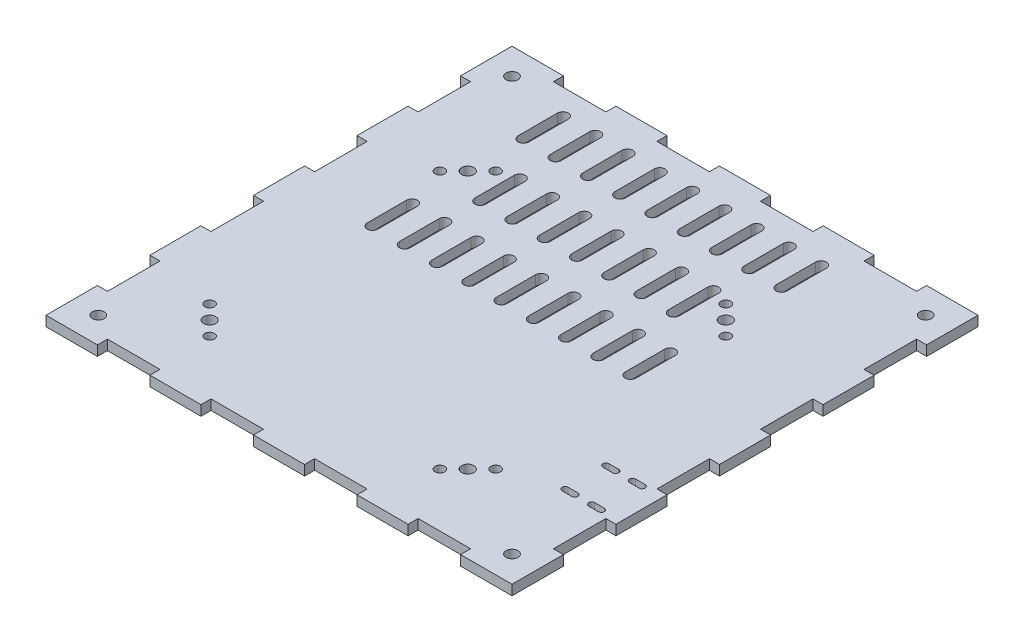
SolidWorks part; units mm, degrees
material "Acrylic (Medium-high impact)"
ref_plane "Front Plane" through (0, 0, 0) normal (0, 0, 1) x (1, 0, 0)
ref_plane "Top Plane" through (0, 0, 0) normal (0, 1, 0) x (1, 0, 0)
ref_plane "Right Plane" through (0, 0, 0) normal (1, 0, 0) x (0, 0, -1)
sketch "Board refrence" plane through (0, 0, 0) normal (0, 1, 0) x (1, 0, 0)
  line L0 (42.5, -17.26) -> (47.5, -17.26)
  line L1 (-40, -40) -> (40, -40)
  line L2 (-40, -40) -> (-40, 40)
  line L3 (-40, 40) -> (40, 40)
  line L4 (40, -40) -> (40, 40)
  line L5 (-40, -40) -> (40, 40) construction
  line L6 (-40, 40) -> (40, -40) construction
  line L7 (-50.8, 46.35) -> (50.8, 46.35)
  line L8 (-50.8, 46.35) -> (-50.8, 40)
  line L9 (-50.8, 40) -> (50.8, 40)
  line L10 (50.8, 46.35) -> (50.8, 40)
  line L11 (42.5, -25.26) -> (47.5, -25.26)
  line L12 (45, -25.26) -> (45, -17.26) construction
  circle A0 centre (-36, 36) radius 1.6
  circle A1 centre (-36, -36) radius 1.6
  circle A2 centre (36, -36) radius 1.6
  circle A3 centre (36, 36) radius 1.6
  point P0 (0, 0)
  point P14 (0, 40)
  point P15 (0, 40)
  point P26 (45, -21.26)
  dimension "D4" = 3.2
  dimension "D1" = 80
  dimension "D2" = 80
  dimension "D3" = 4
  dimension "D5" = 6.35
  dimension "D6" = 101.6
  dimension "D7" = 18.74
  dimension "D8" = 8
  dimension "D9" = 5
  dimension "D10" = 5
sketch "Sketch2" plane through (0, 0, 0) normal (0, 1, 0) x (1, 0, 0)
  line L0 (-40, -40) -> (-40, 40) construction
  line L1 (-56.8, 69.15) -> (66.8, 69.15) construction
  line L2 (-56.8, 69.15) -> (-56.8, -54.45) construction
  line L3 (-56.8, -54.45) -> (66.8, -54.45) construction
  line L4 (66.8, 69.15) -> (66.8, -54.45) construction
  line L6 (40, -40) -> (40, 40) construction
  line L7 (-50.8, 46.35) -> (50.8, 46.35) construction
  line L8 (-60, 72.35) -> (-60, -57.65)
  line L9 (-60, -57.65) -> (70, -57.65)
  line L10 (70, 72.35) -> (70, -57.65)
  line L11 (-60, 72.35) -> (70, 72.35)
  circle A0 centre (-36, 36) radius 1.7
  circle A1 centre (-36, -36) radius 1.7
  circle A2 centre (36, -36) radius 1.7
  circle A3 centre (36, 36) radius 1.7
  point P16 (0, 0)
  dimension "D1" = 3.4
  dimension "D2" = 20
  dimension "D3" = 26
  dimension "D4" = 30
  dimension "D6" = 130
  dimension "D7" = 130
  dimension "D5" = 3.2
extrude "Boss-Extrude1" add sketch "Sketch2" along normal blind 2.8
sketch "Sketch5" plane through (0, 2.8, 0) normal (0, 1, 0) x (1, 0, 0)
  line L0 (32.1109, 39.8891) -> (39.8891, 32.1109) construction
  line L1 (70, -57.65) -> (70, 72.35) construction
  circle A0 centre (39.8891, 32.1109) radius 1.35
  circle A1 centre (32.1109, 39.8891) radius 1.35
  circle A2 centre (32.1109, -39.8891) radius 1.35
  circle A3 centre (39.8891, -32.1109) radius 1.35
  circle A4 centre (-39.8891, -32.1109) radius 1.35
  circle A5 centre (-32.1109, -39.8891) radius 1.35
  circle A6 centre (-32.1109, 39.8891) radius 1.35
  circle A7 centre (-39.8891, 32.1109) radius 1.35
  point P4 (36, 36)
  point P23 (0, 0)
  dimension "D3" = 2.7
  dimension "D1" = 45
  dimension "D2" = 11
extrude "Cut-Extrude2" cut sketch "Sketch5" against normal up to next
sketch "Sketch4" plane through (0, 2.8, 0) normal (0, 1, 0) x (1, 0, 0)
  line L0 (70, 57.9056) -> (70, 43.4611)
  line L1 (70, -57.65) -> (70, 72.35) construction
  line L2 (70, 14.5722) -> (67.2, 14.5722)
  line L3 (67.2, 14.5722) -> (67.2, 29.0167)
  line L4 (67.2, 29.0167) -> (70, 29.0167)
  line L5 (70, 29.0167) -> (70, 14.5722)
  line L6 (70, -14.3167) -> (67.2, -14.3167)
  line L7 (67.2, -14.3167) -> (67.2, 0.1278)
  line L8 (67.2, 0.1278) -> (70, 0.1278)
  line L9 (70, 0.1278) -> (70, -14.3167)
  line L10 (70, 43.4611) -> (67.2, 43.4611)
  line L11 (67.2, 43.4611) -> (67.2, 57.9056)
  line L12 (67.2, 57.9056) -> (70, 57.9056)
  line L13 (70, -43.2056) -> (67.2, -43.2056)
  line L14 (67.2, -43.2056) -> (67.2, -28.7611)
  line L15 (67.2, -28.7611) -> (70, -28.7611)
  line L16 (70, -28.7611) -> (70, -43.2056)
  line L17 (70, 43.4611) -> (70, 14.5722) construction
  line L18 (67.2, -43.2056) -> (67.2, -57.65) construction
  line L19 (-60, -57.65) -> (70, -57.65) construction
  line L20 (67.2, -28.7611) -> (67.2, -14.3167) construction
  line L21 (70, 72.35) -> (-60, 72.35) construction
  line L42 (-60, 72.35) -> (70, -57.65) construction
  line L66 (-45.5556, -57.65) -> (-45.5556, -54.85)
  line L67 (-45.5556, -54.85) -> (-31.1111, -54.85)
  line L68 (-31.1111, -54.85) -> (-31.1111, -57.65)
  line L91 (67.2, 0.1278) -> (67.2, 14.5722) construction
  line L92 (67.2, 29.0167) -> (67.2, 43.4611) construction
  line L93 (67.2, 57.9056) -> (67.2, 72.35) construction
  line L94 (-31.1111, -57.65) -> (-45.5556, -57.65)
  line L95 (-16.6667, -57.65) -> (-16.6667, -54.85)
  line L96 (-16.6667, -54.85) -> (-2.2222, -54.85)
  line L97 (-2.2222, -54.85) -> (-2.2222, -57.65)
  line L103 (-2.2222, -57.65) -> (-16.6667, -57.65)
  line L108 (12.2222, -57.65) -> (12.2222, -54.85)
  line L113 (12.2222, -54.85) -> (26.6667, -54.85)
  line L118 (26.6667, -54.85) -> (26.6667, -57.65)
  line L119 (26.6667, -57.65) -> (12.2222, -57.65)
  line L120 (55.5556, -57.65) -> (41.1111, -57.65)
  line L121 (41.1111, -57.65) -> (41.1111, -54.85)
  line L125 (41.1111, -54.85) -> (55.5556, -54.85)
  line L126 (55.5556, -54.85) -> (55.5556, -57.65)
  line L127 (-60, 57.9056) -> (-57.2, 57.9056)
  line L128 (-57.2, 57.9056) -> (-57.2, 43.4611)
  line L129 (-57.2, 43.4611) -> (-60, 43.4611)
  line L130 (-60, 43.4611) -> (-60, 57.9056)
  line L131 (-60, 29.0167) -> (-57.2, 29.0167)
  line L132 (-57.2, 29.0167) -> (-57.2, 14.5722)
  line L133 (-57.2, 14.5722) -> (-60, 14.5722)
  line L134 (-60, 14.5722) -> (-60, 29.0167)
  line L135 (-60, 0.1278) -> (-57.2, 0.1278)
  line L136 (-57.2, 0.1278) -> (-57.2, -14.3167)
  line L137 (-57.2, -14.3167) -> (-60, -14.3167)
  line L138 (-60, -14.3167) -> (-60, 0.1278)
  line L139 (-60, -43.2056) -> (-60, -28.7611)
  line L140 (-60, -28.7611) -> (-57.2, -28.7611)
  line L141 (-57.2, -28.7611) -> (-57.2, -43.2056)
  line L142 (-57.2, -43.2056) -> (-60, -43.2056)
  line L143 (55.5556, 72.35) -> (55.5556, 69.55)
  line L144 (55.5556, 69.55) -> (41.1111, 69.55)
  line L145 (41.1111, 69.55) -> (41.1111, 72.35)
  line L146 (41.1111, 72.35) -> (55.5556, 72.35)
  line L147 (26.6667, 72.35) -> (26.6667, 69.55)
  line L148 (26.6667, 69.55) -> (12.2222, 69.55)
  line L149 (12.2222, 69.55) -> (12.2222, 72.35)
  line L150 (12.2222, 72.35) -> (26.6667, 72.35)
  line L151 (-2.2222, 72.35) -> (-2.2222, 69.55)
  line L152 (-2.2222, 69.55) -> (-16.6667, 69.55)
  line L153 (-16.6667, 69.55) -> (-16.6667, 72.35)
  line L154 (-16.6667, 72.35) -> (-2.2222, 72.35)
  line L155 (-45.5556, 72.35) -> (-31.1111, 72.35)
  line L156 (-31.1111, 72.35) -> (-31.1111, 69.55)
  line L157 (-31.1111, 69.55) -> (-45.5556, 69.55)
  line L158 (-45.5556, 69.55) -> (-45.5556, 72.35)
  point P27 (5, 7.35)
  point P81 (5, 7.35)
  dimension "D4" = 2.8
  dimension "D1" = 4
  dimension "D2" = 4
extrude "Cut tabs" cut sketch "Sketch4" against normal through all
sketch "Pad reference" plane through (0, 2.8, 0) normal (0, 1, 0) x (1, 0, 0)
  line L2 (-60, -57.65) -> (-45.5556, -57.65) construction
  line L3 (55, 57.35) -> (-45, 57.35) construction
  line L4 (55, 57.35) -> (55, -42.65) construction
  line L5 (55, -42.65) -> (-45, -42.65) construction
  line L7 (-45, 57.35) -> (-45, -42.65) construction
  line L151 (70, -57.65) -> (70, -43.2056) construction
  line L152 (70, 72.35) -> (55.5556, 72.35) construction
  circle A0 centre (-45, 57.35) radius 4
  circle A1 centre (55, 57.35) radius 4
  circle A2 centre (55, -42.65) radius 4
  circle A3 centre (-45, -42.65) radius 4
  dimension "D1" = 8
  dimension "D3" = 15
  dimension "D4" = 15
  dimension "D2" = 15
sketch "Sketch6" plane through (0, 2.8, 0) normal (0, 1, 0) x (1, 0, 0)
  line L0 (64.5, -27.2389) -> (61.8, -27.2389) construction
  line L1 (64.5, -28.0889) -> (61.8, -28.0889)
  line L2 (64.5, -26.3889) -> (61.8, -26.3889)
  line L3 (57.1, -27.2389) -> (54.4, -27.2389) construction
  line L4 (57.1, -28.0889) -> (54.4, -28.0889)
  line L5 (57.1, -26.3889) -> (54.4, -26.3889)
  line L6 (72.5, -21.5389) -> (-49927.5, -21.5389) construction
  line L7 (70, -28.7611) -> (70, -14.3167) construction
  line L8 (57.1, -15.8389) -> (54.4, -15.8389) construction
  line L9 (57.1, -14.9889) -> (54.4, -14.9889)
  line L10 (57.1, -16.6889) -> (54.4, -16.6889)
  line L11 (64.5, -15.8389) -> (61.8, -15.8389) construction
  line L12 (64.5, -14.9889) -> (61.8, -14.9889)
  line L13 (64.5, -16.6889) -> (61.8, -16.6889)
  arc A0 (64.5, -28.0889) -> (64.5, -26.3889) centre (64.5, -27.2389) ccw
  arc A1 (61.8, -26.3889) -> (61.8, -28.0889) centre (61.8, -27.2389) ccw
  arc A2 (57.1, -28.0889) -> (57.1, -26.3889) centre (57.1, -27.2389) ccw
  arc A3 (54.4, -26.3889) -> (54.4, -28.0889) centre (54.4, -27.2389) ccw
  arc A4 (57.1, -14.9889) -> (57.1, -16.6889) centre (57.1, -15.8389) cw
  arc A5 (54.4, -16.6889) -> (54.4, -14.9889) centre (54.4, -15.8389) cw
  arc A6 (64.5, -14.9889) -> (64.5, -16.6889) centre (64.5, -15.8389) cw
  arc A7 (61.8, -16.6889) -> (61.8, -14.9889) centre (61.8, -15.8389) cw
  point P2 (63.15, -27.2389)
  point P7 (55.75, -27.2389)
  point P18 (70, -21.5389)
  point P21 (55.75, -15.8389)
  point P28 (63.15, -15.8389)
  dimension "D3" = 3
  dimension "D1" = 4.4
  dimension "D2" = 1.7
  dimension "D4" = 4.85
  dimension "D5" = 5.5
extrude "Power cord slots" cut sketch "Sketch6" against normal up to next
sketch "Sketch7" plane through (0, 2.8, 0) normal (0, 1, 0) x (1, 0, 0)
  line L0 (-36, 62.55) -> (-36, 51.55) construction
  line L1 (-34.5, 62.55) -> (-34.5, 51.55)
  line L2 (-37.5, 62.55) -> (-37.5, 51.55)
  line L3 (-45.5556, 69.55) -> (-31.1111, 69.55) construction
  line L4 (-37.5, 20.45) -> (-37.5, 9.45)
  line L5 (-28.5, 62.55) -> (-28.5, 51.55)
  line L6 (-25.5, 62.55) -> (-25.5, 51.55)
  line L7 (-27, 62.55) -> (-27, 51.55) construction
  line L8 (-19.5, 62.55) -> (-19.5, 51.55)
  line L9 (-16.5, 62.55) -> (-16.5, 51.55)
  line L10 (-18, 62.55) -> (-18, 51.55) construction
  line L11 (-10.5, 62.55) -> (-10.5, 51.55)
  line L12 (-7.5, 62.55) -> (-7.5, 51.55)
  line L13 (-9, 62.55) -> (-9, 51.55) construction
  line L14 (-1.5, 62.55) -> (-1.5, 51.55)
  line L15 (1.5, 62.55) -> (1.5, 51.55)
  line L16 (0, 62.55) -> (0, 51.55) construction
  line L17 (7.5, 62.55) -> (7.5, 51.55)
  line L18 (10.5, 62.55) -> (10.5, 51.55)
  line L19 (9, 62.55) -> (9, 51.55) construction
  line L20 (16.5, 62.55) -> (16.5, 51.55)
  line L21 (19.5, 62.55) -> (19.5, 51.55)
  line L22 (18, 62.55) -> (18, 51.55) construction
  line L23 (25.5, 62.55) -> (25.5, 51.55)
  line L24 (28.5, 62.55) -> (28.5, 51.55)
  line L25 (27, 62.55) -> (27, 51.55) construction
  line L26 (34.5, 62.55) -> (34.5, 51.55)
  line L27 (37.5, 62.55) -> (37.5, 51.55)
  line L28 (36, 62.55) -> (36, 51.55) construction
  line L32 (-36, 36) -> (-36, 51.55) construction
  line L33 (-36, 36) -> (-36, 20.45) construction
  line L34 (-34.5, 20.45) -> (-34.5, 9.45)
  line L37 (-28.5, 41.5) -> (-28.5, 30.5)
  line L38 (-25.5, 41.5) -> (-25.5, 30.5)
  line L39 (-27, 41.5) -> (-27, 30.5) construction
  line L40 (-19.5, 41.5) -> (-19.5, 30.5)
  line L41 (-16.5, 41.5) -> (-16.5, 30.5)
  line L42 (-18, 41.5) -> (-18, 30.5) construction
  line L43 (-10.5, 41.5) -> (-10.5, 30.5)
  line L44 (-7.5, 41.5) -> (-7.5, 30.5)
  line L45 (-9, 41.5) -> (-9, 30.5) construction
  line L46 (-1.5, 41.5) -> (-1.5, 30.5)
  line L47 (1.5, 41.5) -> (1.5, 30.5)
  line L48 (0, 41.5) -> (0, 30.5) construction
  line L49 (7.5, 41.5) -> (7.5, 30.5)
  line L50 (10.5, 41.5) -> (10.5, 30.5)
  line L51 (9, 41.5) -> (9, 30.5) construction
  line L52 (16.5, 41.5) -> (16.5, 30.5)
  line L53 (19.5, 41.5) -> (19.5, 30.5)
  line L54 (18, 41.5) -> (18, 30.5) construction
  line L55 (25.5, 41.5) -> (25.5, 30.5)
  line L56 (28.5, 41.5) -> (28.5, 30.5)
  line L57 (27, 41.5) -> (27, 30.5) construction
  line L63 (-36, 20.45) -> (-36, 9.45) construction
  line L64 (-28.5, 20.45) -> (-28.5, 9.45)
  line L65 (-25.5, 20.45) -> (-25.5, 9.45)
  line L66 (-27, 20.45) -> (-27, 9.45) construction
  line L67 (-19.5, 20.45) -> (-19.5, 9.45)
  line L68 (-16.5, 20.45) -> (-16.5, 9.45)
  line L69 (-18, 20.45) -> (-18, 9.45) construction
  line L70 (-10.5, 20.45) -> (-10.5, 9.45)
  line L71 (-7.5, 20.45) -> (-7.5, 9.45)
  line L72 (-9, 20.45) -> (-9, 9.45) construction
  line L73 (-1.5, 20.45) -> (-1.5, 9.45)
  line L74 (1.5, 20.45) -> (1.5, 9.45)
  line L75 (0, 20.45) -> (0, 9.45) construction
  line L76 (7.5, 20.45) -> (7.5, 9.45)
  line L77 (10.5, 20.45) -> (10.5, 9.45)
  line L78 (9, 20.45) -> (9, 9.45) construction
  line L79 (16.5, 20.45) -> (16.5, 9.45)
  line L80 (19.5, 20.45) -> (19.5, 9.45)
  line L81 (18, 20.45) -> (18, 9.45) construction
  line L82 (25.5, 20.45) -> (25.5, 9.45)
  line L83 (28.5, 20.45) -> (28.5, 9.45)
  line L84 (27, 20.45) -> (27, 9.45) construction
  line L85 (34.5, 20.45) -> (34.5, 9.45)
  line L86 (37.5, 20.45) -> (37.5, 9.45)
  line L87 (36, 20.45) -> (36, 9.45) construction
  line L88 (34.5, 41.5) -> (34.5, 30.5) [skipped]
  line L89 (37.5, 41.5) -> (37.5, 30.5) [skipped]
  line L90 (-37.5, 41.5) -> (-37.5, 30.5) [skipped]
  line L91 (-34.5, 41.5) -> (-34.5, 30.5) [skipped]
  line L93 (-37.5, 62.55) -> (-28.5, 62.55) construction
  arc A0 (-34.5, 62.55) -> (-37.5, 62.55) centre (-36, 62.55) ccw
  arc A1 (-37.5, 51.55) -> (-34.5, 51.55) centre (-36, 51.55) ccw
  arc A2 (-25.5, 62.55) -> (-28.5, 62.55) centre (-27, 62.55) ccw
  arc A3 (-28.5, 51.55) -> (-25.5, 51.55) centre (-27, 51.55) ccw
  arc A4 (-16.5, 62.55) -> (-19.5, 62.55) centre (-18, 62.55) ccw
  arc A5 (-19.5, 51.55) -> (-16.5, 51.55) centre (-18, 51.55) ccw
  arc A6 (-7.5, 62.55) -> (-10.5, 62.55) centre (-9, 62.55) ccw
  arc A7 (-10.5, 51.55) -> (-7.5, 51.55) centre (-9, 51.55) ccw
  arc A8 (1.5, 62.55) -> (-1.5, 62.55) centre (0, 62.55) ccw
  arc A9 (-1.5, 51.55) -> (1.5, 51.55) centre (0, 51.55) ccw
  arc A10 (10.5, 62.55) -> (7.5, 62.55) centre (9, 62.55) ccw
  arc A11 (7.5, 51.55) -> (10.5, 51.55) centre (9, 51.55) ccw
  arc A12 (19.5, 62.55) -> (16.5, 62.55) centre (18, 62.55) ccw
  arc A13 (16.5, 51.55) -> (19.5, 51.55) centre (18, 51.55) ccw
  arc A14 (28.5, 62.55) -> (25.5, 62.55) centre (27, 62.55) ccw
  arc A15 (25.5, 51.55) -> (28.5, 51.55) centre (27, 51.55) ccw
  arc A16 (37.5, 62.55) -> (34.5, 62.55) centre (36, 62.55) ccw
  arc A17 (34.5, 51.55) -> (37.5, 51.55) centre (36, 51.55) ccw
  arc A20 (-25.5, 41.5) -> (-28.5, 41.5) centre (-27, 41.5) ccw
  arc A21 (-28.5, 30.5) -> (-25.5, 30.5) centre (-27, 30.5) ccw
  arc A22 (-16.5, 41.5) -> (-19.5, 41.5) centre (-18, 41.5) ccw
  arc A23 (-19.5, 30.5) -> (-16.5, 30.5) centre (-18, 30.5) ccw
  arc A24 (-7.5, 41.5) -> (-10.5, 41.5) centre (-9, 41.5) ccw
  arc A25 (-10.5, 30.5) -> (-7.5, 30.5) centre (-9, 30.5) ccw
  arc A26 (1.5, 41.5) -> (-1.5, 41.5) centre (0, 41.5) ccw
  arc A27 (-1.5, 30.5) -> (1.5, 30.5) centre (0, 30.5) ccw
  arc A28 (10.5, 41.5) -> (7.5, 41.5) centre (9, 41.5) ccw
  arc A29 (7.5, 30.5) -> (10.5, 30.5) centre (9, 30.5) ccw
  arc A30 (19.5, 41.5) -> (16.5, 41.5) centre (18, 41.5) ccw
  arc A31 (16.5, 30.5) -> (19.5, 30.5) centre (18, 30.5) ccw
  arc A32 (28.5, 41.5) -> (25.5, 41.5) centre (27, 41.5) ccw
  arc A33 (25.5, 30.5) -> (28.5, 30.5) centre (27, 30.5) ccw
  arc A36 (-34.5, 20.45) -> (-37.5, 20.45) centre (-36, 20.45) ccw
  arc A37 (-37.5, 9.45) -> (-34.5, 9.45) centre (-36, 9.45) ccw
  arc A38 (-25.5, 20.45) -> (-28.5, 20.45) centre (-27, 20.45) ccw
  arc A39 (-28.5, 9.45) -> (-25.5, 9.45) centre (-27, 9.45) ccw
  arc A40 (-16.5, 20.45) -> (-19.5, 20.45) centre (-18, 20.45) ccw
  arc A41 (-19.5, 9.45) -> (-16.5, 9.45) centre (-18, 9.45) ccw
  arc A42 (-7.5, 20.45) -> (-10.5, 20.45) centre (-9, 20.45) ccw
  arc A43 (-10.5, 9.45) -> (-7.5, 9.45) centre (-9, 9.45) ccw
  arc A44 (1.5, 20.45) -> (-1.5, 20.45) centre (0, 20.45) ccw
  arc A45 (-1.5, 9.45) -> (1.5, 9.45) centre (0, 9.45) ccw
  arc A46 (10.5, 20.45) -> (7.5, 20.45) centre (9, 20.45) ccw
  arc A47 (7.5, 9.45) -> (10.5, 9.45) centre (9, 9.45) ccw
  arc A48 (19.5, 20.45) -> (16.5, 20.45) centre (18, 20.45) ccw
  arc A49 (16.5, 9.45) -> (19.5, 9.45) centre (18, 9.45) ccw
  arc A50 (28.5, 20.45) -> (25.5, 20.45) centre (27, 20.45) ccw
  arc A51 (25.5, 9.45) -> (28.5, 9.45) centre (27, 9.45) ccw
  arc A52 (37.5, 20.45) -> (34.5, 20.45) centre (36, 20.45) ccw
  arc A53 (34.5, 9.45) -> (37.5, 9.45) centre (36, 9.45) ccw
  arc A54 (37.5, 41.5) -> (34.5, 41.5) centre (36, 41.5) ccw [skipped]
  arc A55 (34.5, 30.5) -> (37.5, 30.5) centre (36, 30.5) ccw [skipped]
  arc A56 (-34.5, 41.5) -> (-37.5, 41.5) centre (-36, 41.5) ccw [skipped]
  arc A57 (-37.5, 30.5) -> (-34.5, 30.5) centre (-36, 30.5) ccw [skipped]
  point P2 (-36, 57.05)
  point P12 (-37.5, 57.05)
  point P16 (-27, 57.05)
  point P23 (-18, 57.05)
  point P30 (-9, 57.05)
  point P37 (0, 57.05)
  point P44 (9, 57.05)
  point P51 (18, 57.05)
  point P58 (27, 57.05)
  point P65 (36, 57.05)
  point P86 (-27, 36)
  point P93 (-18, 36)
  point P100 (-9, 36)
  point P107 (0, 36)
  point P114 (9, 36)
  point P121 (18, 36)
  point P128 (27, 36)
  point P140 (-36, 14.95)
  point P149 (-27, 14.95)
  point P156 (-18, 14.95)
  point P163 (-9, 14.95)
  point P170 (0, 14.95)
  point P177 (9, 14.95)
  point P184 (18, 14.95)
  point P191 (27, 14.95)
  point P198 (36, 14.95)
  dimension "D1" = 7
  dimension "D2" = 11
  dimension "D4" = 3
  dimension "D7" = 9
  dimension "D5" = 9
  dimension "D6" = 3
extrude "Cooling slots" cut sketch "Sketch7" against normal up to next (2.8 mm away)
sketch "Sketch8" plane through (0, 2.8, 0) normal (0, 1, 0) x (1, 0, 0)
  line L1 (-60, 72.35) -> (70, 72.35) construction
  line L2 (-60, 72.35) -> (-60, -57.65) construction
  line L3 (-60, -57.65) -> (70, -57.65) construction
  line L4 (70, 72.35) -> (70, -57.65) construction
  line L72 (-52.7, 65.05) -> (-52.7, -50.35) construction
  line L73 (-52.7, -50.35) -> (62.7, -50.35) construction
  line L74 (62.7, 65.05) -> (62.7, -50.35) construction
  line L75 (-52.7, 65.05) -> (62.7, 65.05) construction
  circle A0 centre (-52.7, 65.05) radius 1.65
  circle A1 centre (62.7, 65.05) radius 1.65
  circle A2 centre (62.7, -50.35) radius 1.65
  circle A3 centre (-52.7, -50.35) radius 1.65
  dimension "D1" = 3.3
  dimension "D2" = 7.3
extrude "Cornerpiece holes" cut sketch "Sketch8" against normal up to next
other "Tolerance" flip direction yes face at (41.1111, 1.4, -70.95) face at (12.2222, 1.4, -70.95) face at (-16.6667, 1.4, -70.95) face at (-45.5556, 1.4, -70.95) face at (26.6667, 1.4, -70.95) face at (55.5556, 1.4, -70.95) face at (-2.2222, 1.4, -70.95) face at (-31.1111, 1.4, -70.95) face at (-58.6, 1.4, -43.4611) face at (-58.6, 1.4, -57.9056) face at (-58.6, 1.4, -14.5722) face at (-58.6, 1.4, -29.0167) face at (-58.6, 1.4, -0.1278) face at (-58.6, 1.4, 14.3167) face at (-58.6, 1.4, 43.2056) face at (-58.6, 1.4, 28.7611) face at (-31.1111, 1.4, 56.25) face at (-45.5556, 1.4, 56.25) face at (-16.6667, 1.4, 56.25) face at (-2.2222, 1.4, 56.25) face at (12.2222, 1.4, 56.25) face at (26.6667, 1.4, 56.25) face at (55.5556, 1.4, 56.25) face at (41.1111, 1.4, 56.25) face at (68.6, 1.4, 28.7611) face at (68.6, 1.4, 43.2056) face at (68.6, 1.4, 14.3167) face at (68.6, 1.4, -0.1278) face at (68.6, 1.4, -14.5722) face at (68.6, 1.4, -29.0167) face at (68.6, 1.4, -57.9056) face at (68.6, 1.4, -43.4611) offset 0.1 parameters "D1"=0.1
equation "\"D5@Board refrence\" =  ( 1 / 4 )  * 1in"
equation "\"D6@Board refrence\" = 4in"
equation "\"slot_depth\"= 2.8mm"
equation "\"slot_width_tolerance\"= 0.0mm"
equation "\"D4@Sketch4\"=\"slot_depth\""
equation "\"D2@Sketch8\"=4.50+2.8"
